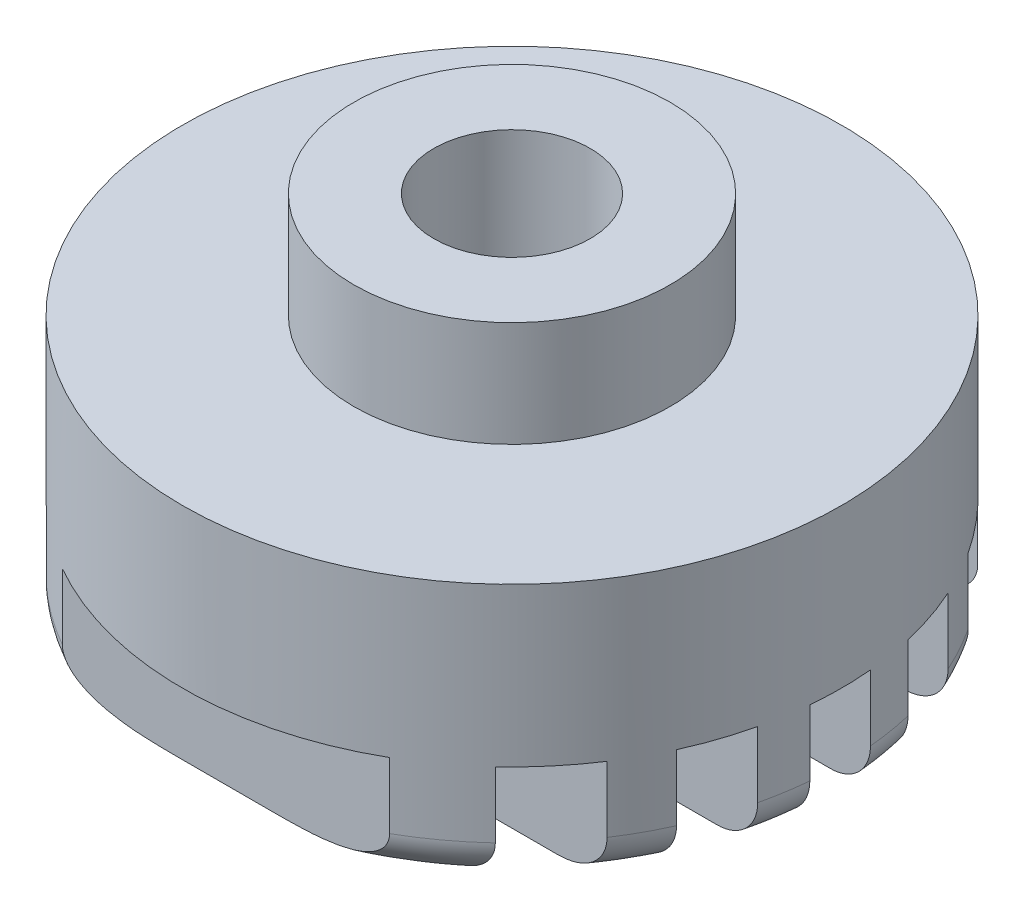
SolidWorks part; units mm, degrees
ref_plane "Front Plane" through (0, 0, 0) normal (0, 0, 1) x (1, 0, 0)
ref_plane "Top Plane" through (0, 0, 0) normal (0, 1, 0) x (1, 0, 0)
ref_plane "Right Plane" through (0, 0, 0) normal (1, 0, 0) x (0, 0, -1)
sketch "Sketch1" plane through (0, 0, 0) normal (0, 1, 0) x (1, 0, 0)
  circle A0 centre (0, 0) radius 25
  dimension "D1" = 50
extrude "Boss-Extrude1" add sketch "Sketch1" along normal blind 20
sketch "Sketch14" plane through (0, 0, 0) normal (0, 1, 0) x (1, 0, 0)
  line L1 (-26.93, 2.2997) -> (26.93, 2.2997)
  line L2 (-26.93, 2.2997) -> (-26.93, -2.2997)
  line L3 (-26.93, -2.2997) -> (26.93, -2.2997)
  line L4 (26.93, 2.2997) -> (26.93, -2.2997)
  line L5 (-26.93, 2.2997) -> (26.93, -2.2997) construction
  line L6 (-26.93, -2.2997) -> (26.93, 2.2997) construction
  point P0 (0, 0)
extrude "Cut-Extrude13" cut sketch "Sketch14" along normal blind 8
pattern_linear "LPattern11" count 4 spacing 8 along (0, 0, 1) count 4 spacing 8 along (0, 0, -1) of "Cut-Extrude13"
sketch "Sketch16" plane through (0, 20, 0) normal (0, 1, 0) x (1, 0, 0)
  circle A0 centre (0, 0) radius 12
  circle A1 centre (0, 0) radius 12
  dimension "D1" = 24
sketch "Sketch18" plane through (0, 0, 0) normal (0, -1, 0) x (1, 0, 0)
  circle A0 centre (0, 0) radius 10.0316
extrude "Cut-Extrude15" cut sketch "Sketch18" against normal blind 8
extrude "Boss-Extrude3" add sketch "Sketch16" along normal blind 8 contours A0
sketch "Sketch19" plane through (0, 28, 0) normal (0, 1, 0) x (1, 0, 0)
  circle A0 centre (0, 0) radius 5.9349
extrude "Cut-Extrude16" cut sketch "Sketch19" against normal blind 26
fillet "Fillet2" radius 3 1 edges at (-14.8211, 0, 20.1329)
fillet "Fillet3" radius 3 11 edges at (14.8211, 0, -20.1329) (21.9118, 0, -12.0363) (24.6764, 0, -4.0095) (24.6764, 0, 4.0095) (21.9118, 0, 12.0363) (14.8211, 0, 20.1329) (-14.8211, 0, -20.1329) (-21.9118, 0, -12.0363) (-24.6764, 0, -4.0095) (-24.6764, 0, 4.0095) (-21.9118, 0, 12.0363)
